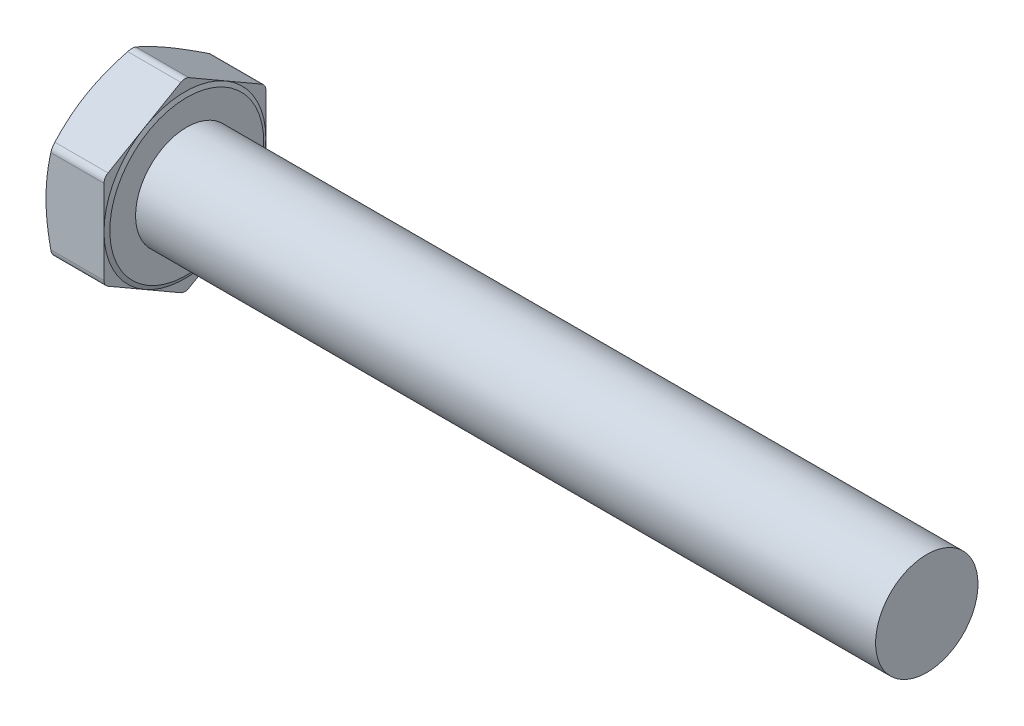
SolidWorks part; units mm, degrees
ref_plane "Front Plane" through (0, 0, 0) normal (0, 0, 1) x (1, 0, 0)
ref_plane "Top Plane" through (0, 0, 0) normal (0, 1, 0) x (1, 0, 0)
ref_plane "Right Plane" through (0, 0, 0) normal (1, 0, 0) x (0, 0, -1)
sketch "Sketch1" plane through (0, 0, 0) normal (0, 0, 1) x (1, 0, 0)
  line L0 (0, 0) -> (50.8, 0) construction
  line L1 (0, 0) -> (-4.3656, 0) construction
  line L2 (0, 5.5562) -> (0, -5.5562) construction
  line L3 (-4.3656, 5.5562) -> (-4.3656, -5.5563) construction
  line L4 (50.8, 3.175) -> (50.8, -3.175) construction
  line L8 (49.53, 3.175) -> (50.8, 3.175) construction
  point P8 (49.53, 0)
  point P11 (46.355, -3.175)
  point P12 (1.27, 0)
  point P13 (10.16, 0)
  point P14 (37.465, 0)
  dimension "Head Height" = 4.3656
  dimension "Head Width" = 11.1125
  dimension "Length" = 50.8
  dimension "Thread Size" = 6.35
  dimension "D1" = 4.445
  dimension "Thread Pitch" = 1.27
  dimension "D2" = 1.27
  dimension "D3" = 8.89
  dimension "D4" = 8.89
sketch "Sketch2" plane through (0, 0, 0) normal (1, 0, 0) x (0, 0, -1)
  circle A0 centre (0, 0) radius 3.175
extrude "Boss-Extrude1" add sketch "Sketch2" along normal up to vertex (50.8 mm away) up to point (50.8, 3.175, 0)
sketch "Sketch3" plane through (0, 0, 0) normal (-1, 0, 0) x (0, 0, 1)
  line L0 (0, 6.4158) -> (0, 0) construction
  line L1 (0, 6.4158) -> (-5.5562, 3.2079)
  line L2 (-5.5562, 3.2079) -> (-5.5562, -3.2079)
  line L3 (-5.5562, -3.2079) -> (0, -6.4158)
  line L4 (0, -6.4158) -> (5.5562, -3.2079)
  line L5 (5.5562, -3.2079) -> (5.5562, 3.2079)
  line L6 (5.5562, 3.2079) -> (0, 6.4158)
  circle A0 centre (0, 0) radius 5.5562 construction
extrude "Boss-Extrude2" add sketch "Sketch3" along normal up to vertex (4.3656 mm away) up to point (-4.3656, 5.5562, 0)
sketch "Sketch5" plane through (-4.3656, 0, 0) normal (-1, 0, 0) x (0, 0, 1)
  circle A0 centre (0, 0) radius 5.5562 construction
  circle A1 centre (0, 0) radius 5.5562 construction
  circle A2 centre (0, 0) radius 5.0006
  dimension "D1" = 0.5556
extrude "Cut-Extrude1" cut sketch "Sketch5" against normal up to vertex (4.3656 mm away) draft 65 flip side to cut up to point (0, 0, 0)
sketch "Sketch11" plane through (-4.3656, 0, 0) normal (-1, 0, 0) x (0, 0, 1)
  line L0 (0, 3.9449) -> (0, 2.4447) construction
  line L1 (0.2223, 3.9449) -> (0.2223, 2.4447)
  line L2 (-0.2222, 3.9449) -> (-0.2222, 2.4447)
  arc A0 (0.2223, 3.9449) -> (-0.2222, 3.9449) centre (0, 3.9449) ccw
  arc A1 (-0.2222, 2.4447) -> (0.2223, 2.4447) centre (0, 2.4447) ccw
  circle A2 centre (0, 0) radius 4.1672 construction
  circle A3 centre (0, 0) radius 2.2225 construction
  point P3 (0, 3.1948)
  dimension "D1" = 8.3344
  dimension "D2" = 4.445
  dimension "D3" = 0.4445
extrude "Boss-Extrude5" add sketch "Sketch11" along normal blind 0.0635
fillet "Fillet5" radius 0.0635 4 edges at (-4.4291, 3.1948, 0.2223) (-4.4291, 2.2225, 0) (-4.4291, 3.1948, -0.2222) (-4.4291, 4.1672, 0)
pattern_circular "CirPattern1" count 6 over 360 about axis through (0, 0, 0) along (-1, 0, 0) of "Boss-Extrude5", "Fillet5" reverse direction yes
fillet "Fillet7" radius 0.5556 6 edges at (-1.8529, -6.4158, 0) (-1.8529, -3.2079, -5.5562) (-1.8529, 3.2079, -5.5562) (-1.8529, 6.4158, 0) (-1.8529, -3.2079, 5.5562) (-1.8529, 3.2079, 5.5562)
chamfer "Chamfer1" distance 0.9525 angle 45 1 edges at (50.8, 0, -3.175)
sketch "Sketch15" plane through (0, 0, 0) normal (0, 0, 1) x (1, 0, 0)
  line L0 (0, 5.2839) -> (-0.127, 5.5562)
  line L1 (0, 5.5562) -> (0, -5.5562) construction
  line L2 (-0.127, 5.5562) -> (-0.127, 6.4158)
  line L3 (-0.127, 6.4158) -> (0, 6.4158)
  line L4 (0, 6.4158) -> (0, 5.2839)
  dimension "D1" = 0.127
  dimension "D2" = 25
revolve "Cut-Revolve1" cut sketch "Sketch15" angle 360 about L1
fillet "Fillet4" radius 0.3175 1 edges at (0, 0, 3.175)
sketch "Reference Sketch1" plane through (0, 0, 0) normal (1, 0, 0) x (0, 0, -1)
  line L1 (0, 6.4158) -> (-5.5562, 3.2079)
  line L2 (-5.5562, 3.2079) -> (-5.5563, -3.2079)
  line L3 (-5.5563, -3.2079) -> (0, -6.4158)
  line L4 (0, -6.4158) -> (5.5562, -3.2079)
  line L5 (5.5562, -3.2079) -> (5.5563, 3.2079)
  line L6 (5.5563, 3.2079) -> (0, 6.4158)
  circle A0 centre (0, 0) radius 5.5562 construction
  circle A1 centre (0, 0) radius 5.5562
sketch "Sketch12" plane through (50.8, 0, 0) normal (1, 0, 0) x (0, 0, -1)
  circle A1 centre (0, 0) radius 3.175
ref_plane "Plane2" through (1.27, 0, 0) normal (1, 0, 0) x (0, 0, -1)
split "Split1" trim tools "Plane2" bodies to split 126 116 resulting bodies 118 119
curve "Helix/Spiral2" pitch 1.27 height 52.07 radius 3.175 centre (50.8, 0, 0) axis (-1, 0, 0) start towards (0, 1, 0) parameters "Pitch"=1.27
sketch "Sketch13" plane through (0, 0, 0) normal (0, 0, 1) x (1, 0, 0)
  line L0 (50.7206, 3.3125) -> (51.3556, 2.2126) construction
  line L1 (51.3556, 2.2126) -> (51.9906, 3.3125) construction
  line L2 (51.9906, 3.3125) -> (50.7206, 3.3125) construction
  line L3 (51.3556, 2.2126) -> (51.3556, 2.3501) construction
  line L4 (50.8, 3.175) -> (51.9113, 3.175) construction
  line L5 (51.3556, 3.175) -> (51.3556, 3.3125) construction
  line L6 (51.435, 2.3501) -> (51.9509, 3.2437)
  line L7 (51.435, 2.3501) -> (51.2763, 2.3501)
  line L8 (51.9509, 3.2437) -> (50.7603, 3.2437)
  line L9 (49.53, 3.175) -> (50.8, 3.175) construction
  line L10 (50.7603, 3.2437) -> (51.2763, 2.3501)
  point P15 (51.3556, 3.2437)
  dimension "D1" = 0.1588
sweep "Cut-Sweep1" cut profiles "Sketch13" path "Helix/Spiral2" align with end faces yes
sketch "Sketch14" plane through (1.27, 0, 0) normal (1, 0, 0) x (0, 0, -1)
  circle A1 centre (0, 0) radius 3.175
  circle A2 centre (0, 0) radius 3.175
  dimension "D1" = 0
extrude "Boss-Extrude4" add sketch "Sketch14" along normal through all draft 50
sketch "Sketch16" plane through (50.8, 0, 0) normal (1, 0, 0) x (0, 0, -1)
  circle A0 centre (0, 0) radius 3.5147
extrude "Boss-Extrude6" add sketch "Sketch16" against normal up to surface (50.8 mm away) up to face at (0, 0, 3.4925)
equation "\"D1@Sketch11\"=\"Head Width@Sketch1\" * 0.75"
equation "\"D2@Sketch11\"=\"Head Width@Sketch1\"*0.4"
equation "\"D3@Sketch11\"=\"Head Width@Sketch1\" * .04"
equation "\"D3@Helix/Spiral2\"=\"Length@Sketch1\" + \"Thread Pitch@Sketch1\""
equation "\"D1@Chamfer1\"=\"Thread Pitch@Sketch1\"*0.750"
equation "\"D1@Sketch1\"=\"Thread Pitch@Sketch1\"*3.5"
equation "\"Pitch@Helix/Spiral2\"=\"Thread Pitch@Sketch1\""
equation "\"D1@Sketch13\"=\"Thread Pitch@Sketch1\"*0.125"
equation "\"D1@Sketch5\"=\"Head Width@Sketch1\"*0.05"
equation "\"D1@Fillet4\"=\"Thread Size@Sketch1\"*0.05"
equation "\"D2@Sketch1\"=\"Thread Pitch@Sketch1\""
equation "\"D1@Fillet7\"=\"Head Width@Sketch1\"*0.05"
equation "\"D3@Sketch1\"=\"D1@Sketch1\"*2"
equation "\"D4@Sketch1\"=\"D1@Sketch1\"*2"
